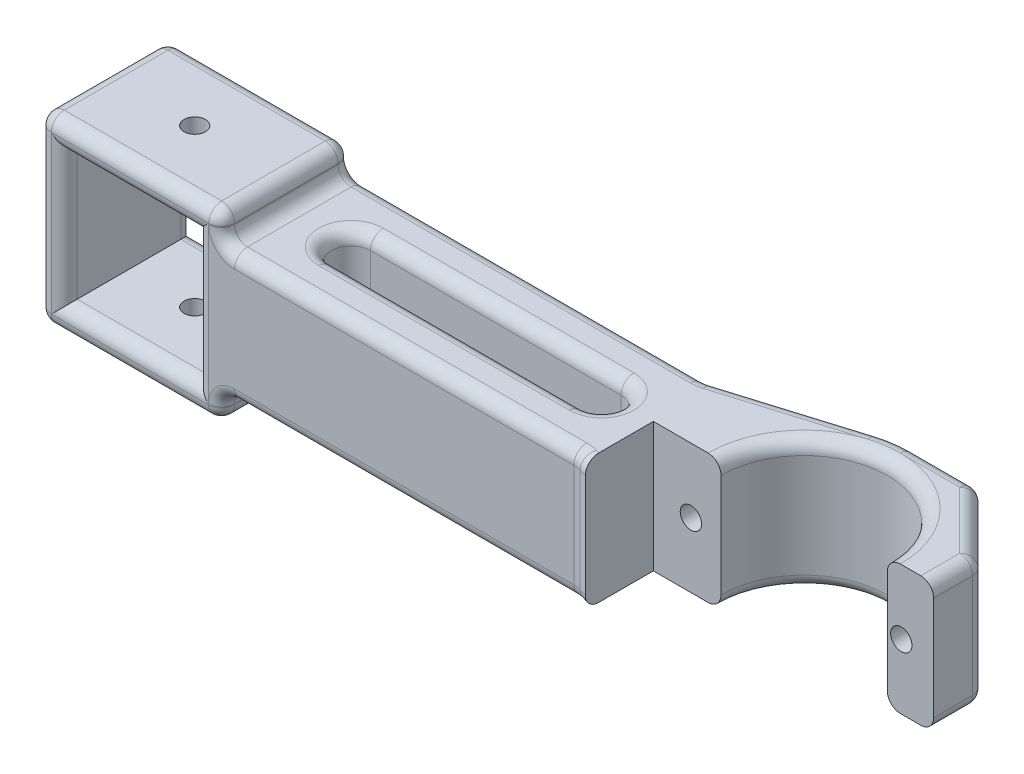
SolidWorks part; units mm, degrees
ref_plane "Front Plane" through (0, 0, 0) normal (0, 0, 1) x (1, 0, 0)
ref_plane "Top Plane" through (0, 0, 0) normal (0, 1, 0) x (1, 0, 0)
ref_plane "Right Plane" through (0, 0, 0) normal (1, 0, 0) x (0, 0, -1)
sketch "Sketch1" plane through (0, 0, 0) normal (0, 0, 1) x (1, 0, 0)
  line L1 (-10.15, -10.15) -> (10.15, -10.15)
  line L2 (-10.15, -10.15) -> (-10.15, 10.15)
  line L3 (-10.15, 10.15) -> (10.15, 10.15)
  line L4 (10.15, -10.15) -> (10.15, 10.15)
  line L5 (-10.15, -10.15) -> (10.15, 10.15) construction
  line L6 (-10.15, 10.15) -> (10.15, -10.15) construction
  point P0 (0, 0)
  dimension "D1" = 20.3
extrude "Extrude-Thin1" add sketch "Sketch1" along normal mid plane 20 thin thin type one direction wall 4
sketch "Sketch2" plane through (0, 0, 0) normal (0, 1, 0) x (1, 0, 0)
  line L3 (14.15, -10) -> (14.15, 10) construction
  line L4 (14.15, 10) -> (69.15, 10)
  line L5 (14.15, 10) -> (14.15, -10)
  line L6 (14.15, -10) -> (69.15, -10)
  line L7 (69.15, 10) -> (69.15, -10)
  line L9 (0, 0) -> (94.15, 0) construction
  line L10 (69.15, -10) -> (89.2407, -16.119)
  line L13 (69.15, 10) -> (89.2407, 16.119)
  line L15 (69.15, -10) -> (69.15, 10)
  circle A2 centre (94.15, 0) radius 12.85
  arc A3 (89.2407, -16.119) -> (89.2407, 16.119) centre (94.15, 0) ccw
  circle A4 centre (94.15, 0) radius 16.85 construction
  point P1 (0, 0)
  dimension "D1" = 25.7
  dimension "D2" = 4
  dimension "D3" = 80
  dimension "D4" = 25
extrude "Boss-Extrude4" add sketch "Sketch2" along normal mid plane 20 contours L7 L4 L5 L6 | L10 A3 L13 L7 A2 region at (41.65, 0, 0) region at (79.3519, 0, -12.5455)
sketch "Sketch3" plane through (0, 0, 0) normal (0, 1, 0) x (1, 0, 0)
  line L0 (94.15, 16.85) -> (114.15, 16.85)
  line L1 (114.15, 16.85) -> (114.15, -16.85)
  line L2 (114.15, -16.85) -> (94.15, -16.85)
  line L3 (14.15, -10) -> (14.15, 10) construction
  arc A1 (94.15, -16.85) -> (94.15, 16.85) centre (94.15, 0) ccw
  arc A2 (89.2407, -16.119) -> (89.2407, 16.119) centre (94.15, 0) ccw construction
  point P3 (94.15, 0)
  point P4 (94.15, 0)
  point P9 (38.539, 0)
  point P10 (0, 0)
  point P13 (39.15, 0)
  point P15 (0, 0)
  dimension "D1" = 100
extrude "Boss-Extrude5" add sketch "Sketch3" along normal mid plane 20
sketch "Sketch4" plane through (0, 0, 0) normal (0, -1, 0) x (1, 0, 0)
  line L9 (104.15, 16.85) -> (114.15, 16.85)
  line L10 (94.15, 16.85) -> (114.15, 16.85) construction
  line L11 (114.15, 16.85) -> (114.15, 6.85)
  line L12 (114.15, 16.85) -> (114.15, -16.85) construction
  line L13 (114.15, 6.85) -> (104.15, 16.85)
  line L14 (114.15, -16.85) -> (104.15, -16.85)
  line L15 (114.15, -16.85) -> (94.15, -16.85) construction
  line L16 (104.15, -16.85) -> (114.15, -6.85)
  line L17 (114.15, -6.85) -> (114.15, -16.85)
  line L18 (0, 0) -> (114.15, 0) construction
  point P13 (114.15, -6.8642)
  point P20 (114.15, 6.8311)
  dimension "D1" = 10
extrude "Cut-Extrude1" cut sketch "Sketch4" against normal through all both and the other way through all contours L13 L9 L11 | L17 L14 L16
sketch "Sketch5" plane through (0, 0, 0) normal (0, 0, 1) x (1, 0, 0)
  line L0 (0, 0) -> (109.15, 0) construction
  line L1 (109.15, 10) -> (109.15, -10) construction
  line L4 (69.15, 10) -> (69.15, -10) construction
  line L5 (104.15, 10) -> (114.15, 10) construction
  circle A0 centre (109.15, 0) radius 1.65
  circle A1 centre (76.65, 0) radius 1.65
  point P6 (109.1814, 0)
  point P7 (109.15, 10)
  dimension "D1" = 3.3
  dimension "D2" = 3.3
  dimension "D3" = 7.5
extrude "Cut-Extrude2" cut sketch "Sketch5" against normal through all both and the other way through all
fillet "Fillet1" radius 2 6 edges at (14.15, -14.15, 0) (-14.15, -14.15, 0) (-14.15, 14.15, 0) (14.15, 14.15, 0) (14.15, -10, 0) (14.15, 10, 0)
fillet "Fillet2" radius 4 2 edges at (69.15, 0, -10) (69.15, 0, 10)
fillet "Fillet3" radius 2 62 edges at (13.5642, 13.5642, 10) (0, 14.15, 10) (-13.5642, 13.5642, 10) (-14.15, 0, 10) (-13.5642, -13.5642, 10) (0, -14.15, 10) (13.5642, -13.5642, 10) (13.5642, -13.5642, -10) (0, -14.15, -10) (-13.5642, -13.5642, -10) (-14.15, 0, -10) (-13.5642, 13.5642, -10) (0, 14.15, -10) (13.5642, 13.5642, -10) (-10.15, 0, -10) (0, -10.15, -10) (10.15, 0, -10) (0, 10.15, -10) (0, 10.15, 10) (-10.15, 0, 10) (0, -10.15, 10) (10.15, 0, 10) (99.15, -10, 16.85) (99.15, 10, 16.85) (99.15, -10, -16.85) (99.15, 10, -16.85) (104.15, 0, 16.85) (114.15, -10, 0) (114.15, 0, 6.85) (114.15, 10, 0) (42.3522, 10, -10) (69.1435, 10, -10.0436) (79.4802, 10, -13.1463) (91.6683, 10, -16.6662) (42.3522, -10, -10) (69.1435, -10, -10.0436) (79.4802, -10, -13.1463) (91.6683, -10, -16.6662) (42.3522, -10, 10) (69.1435, -10, 10.0436) (79.4802, -10, 13.1463) (91.6683, -10, 16.6662) (42.3522, 10, 10) (69.1435, 10, 10.0436) (79.4802, 10, 13.1463) (91.6683, 10, 16.6662) (104.15, 0, -16.85) (114.15, 0, -6.85) (14.7358, 10.5858, -10) (14.15, 12.075, -10) (14.15, -12.075, -10) (14.7358, -10.5858, -10) (14.7358, -10.5858, 10) (14.15, -12.075, 10) (14.15, 12.075, 10) (14.7358, 10.5858, 10) (109.15, 10, -11.85) (109.15, -10, -11.85) (109.15, -10, 11.85) (109.15, 10, 11.85) (94.15, -10, 12.85) (94.15, 10, 12.85)
sketch "Sketch6" plane through (0, 14.15, 0) normal (0, 1, 0) x (1, 0, 0)
  line L0 (0, 8) -> (0, -8) construction
  line L1 (12.15, 8) -> (-12.15, 8) construction
  line L2 (-12.15, -8) -> (12.15, -8) construction
  circle A2 centre (0, 0) radius 1.65
  dimension "D1" = 3.3
extrude "Cut-Extrude4" cut sketch "Sketch6" against normal through all both and the other way through all
sketch "Sketch7" plane through (0, 0, 0) normal (0, 0, 1) x (1, 0, 0)
  circle A0 centre (109.15, 0) radius 3
  circle A1 centre (76.65, 0) radius 3
  dimension "D1" = 6
extrude "Cut-Extrude5" cut sketch "Sketch7" along normal blind 20 from offset 6
sketch "Sketch8" plane through (0, 0, 0) normal (0, 0, 1) x (1, 0, 0)
  line L1 (76.65, 3.2909) -> (73.8, 1.6454)
  line L2 (73.8, 1.6454) -> (73.8, -1.6454)
  line L3 (73.8, -1.6454) -> (76.65, -3.2909)
  line L4 (76.65, -3.2909) -> (79.5, -1.6454)
  line L5 (79.5, -1.6454) -> (79.5, 1.6454)
  line L6 (79.5, 1.6454) -> (76.65, 3.2909)
  line L7 (109.15, 3.2909) -> (106.3, 1.6454)
  line L8 (106.3, 1.6454) -> (106.3, -1.6454)
  line L9 (106.3, -1.6454) -> (109.15, -3.2909)
  line L10 (109.15, -3.2909) -> (112, -1.6454)
  line L11 (112, -1.6454) -> (112, 1.6454)
  line L12 (112, 1.6454) -> (109.15, 3.2909)
  circle A0 centre (76.65, 0) radius 2.85 construction
  circle A1 centre (109.15, 0) radius 2.85 construction
  dimension "D1" = 5.7
extrude "Cut-Extrude6" cut sketch "Sketch8" against normal blind 20 from offset 5 offset against normal yes
sketch "Sketch9" plane through (0, 0, 0) normal (0, 1, 0) x (1, 0, 0)
  line L0 (70.85, 0) -> (114.15, 0)
  line L2 (114.15, 0) -> (114.15, -21.2033)
  line L3 (114.15, -21.2033) -> (70.85, -21.2033)
  line L4 (70.85, -21.2033) -> (70.85, 0)
  line L6 (114.15, 6.0216) -> (114.15, -6.0216) construction
  point P2 (70.3025, 8.2603)
  point P3 (70.3025, -8.2603)
  dimension "D1" = 43.3
extrude "Cut-Extrude7" cut sketch "Sketch9" against normal through all both and the other way through all
sketch "Sketch10" plane through (0, 10, 0) normal (0, 1, 0) x (1, 0, 0)
  line L0 (24.15, 0) -> (62.85, 0) construction
  line L1 (24.15, 3) -> (62.85, 3)
  line L2 (24.15, -3) -> (62.85, -3)
  line L3 (16.15, 8) -> (16.15, -8) construction
  line L4 (70.85, 0) -> (70.85, -8.4271) construction
  arc A0 (24.15, 3) -> (24.15, -3) centre (24.15, 0) ccw
  arc A1 (62.85, -3) -> (62.85, 3) centre (62.85, 0) ccw
  point P3 (43.5, 0)
  dimension "D1" = 8
  dimension "D2" = 8
  dimension "D3" = 6
extrude "Cut-Extrude8" cut sketch "Sketch10" against normal through all both and the other way through all
fillet "Fillet4" radius 2 8 edges at (43.5, -10, -3) (65.85, -10, 0) (43.5, -10, 3) (43.5, 10, -3) (65.85, 10, 0) (43.5, 10, 3) (21.15, -10, 0) (21.15, 10, 0)
